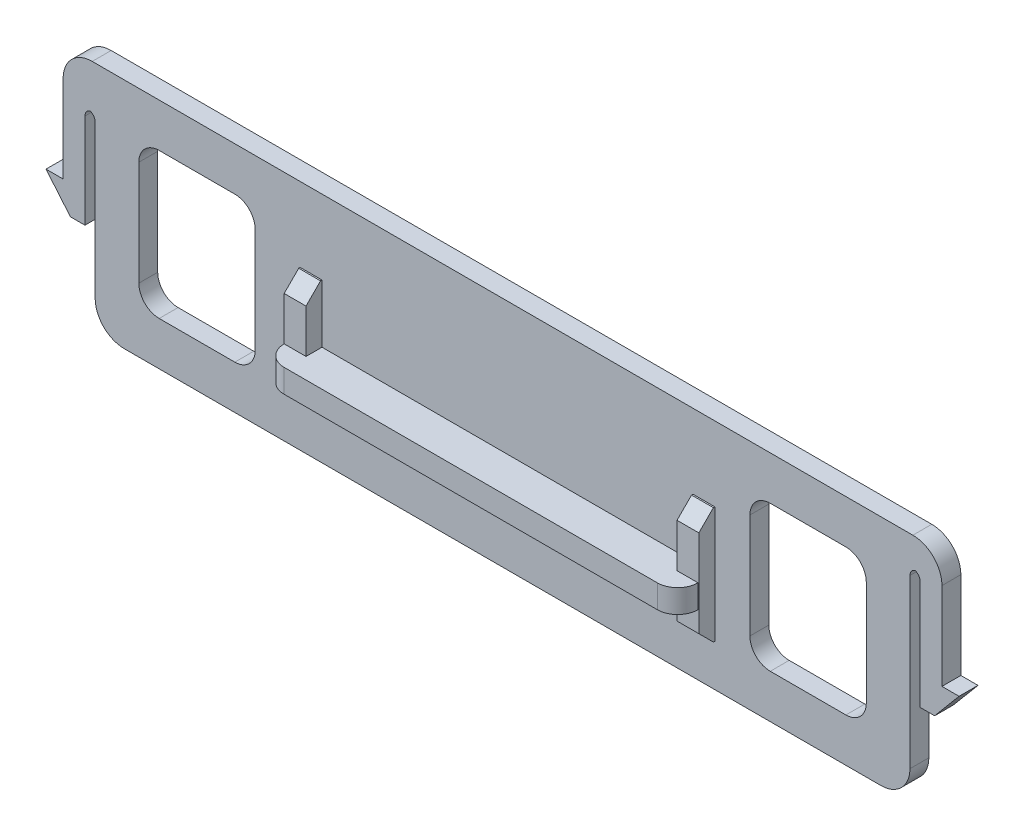
SolidWorks part; units mm, degrees
ref_plane "前视基准面" through (0, 0, 0) normal (0, 0, 1) x (1, 0, 0)
ref_plane "上视基准面" through (0, 0, 0) normal (0, 1, 0) x (1, 0, 0)
ref_plane "右视基准面" through (0, 0, 0) normal (1, 0, 0) x (0, 0, -1)
sketch "草图1" plane through (0, 0, 0) normal (0, 0, 1) x (1, 0, 0)
  line L1 (-28, 8) -> (28, 8)
  line L2 (-28, 8) -> (-28, -8)
  line L3 (-28, -8) -> (28, -8)
  line L4 (28, 8) -> (28, -8)
  line L5 (-28, 8) -> (28, -8) construction
  line L6 (-28, -8) -> (28, 8) construction
  point P0 (0, 0)
  dimension "D1" = 56
  dimension "D2" = 16
extrude "凸台-拉伸1" add sketch "草图1" along normal blind 1.3
sketch "草图2" plane through (0, 0, 1.3) normal (0, 0, 1) x (1, 0, 0)
  line L9 (28, 8) -> (30.2, 8)
  line L10 (30.2, 8) -> (30.2, 0)
  line L11 (30.2, 0) -> (31.7, 0)
  line L12 (31.7, 0) -> (31.7, -2)
  line L13 (31.7, -2) -> (28.7, -2)
  line L14 (28.7, -2) -> (28.7, 6)
  line L15 (28.7, 6) -> (28, 6)
  line L16 (28, -8) -> (28, 8) construction
  line L17 (28, 6) -> (28, 8)
  line L20 (-28, 8) -> (-30.2, 8)
  line L21 (-30.2, 8) -> (-30.2, 0)
  line L22 (-30.2, 0) -> (-31.7, 0)
  line L23 (-31.7, 0) -> (-31.7, -2)
  line L24 (-31.7, -2) -> (-28.7, -2)
  line L25 (-28.7, -2) -> (-28.7, 5)
  line L26 (-28.7, 5) -> (-28, 5)
  line L27 (-28, 8) -> (-28, -8) construction
  line L28 (-28, 5) -> (-28, 8)
  point P2 (0, 0)
  point P12 (-29, 6)
  point P23 (0, 0)
  point P24 (0, 0)
  dimension "D1" = 8
  dimension "D2" = 2
  dimension "D3" = 3
  dimension "D4" = 1.5
  dimension "D5" = 2.2
  dimension "D6" = 1.5
  dimension "D7" = 2.2
  dimension "D8" = 8
  dimension "D9" = 2
  dimension "D10" = 3
  dimension "D11" = 3
  dimension "D12" = 2
extrude "凸台-拉伸2" add sketch "草图2" against normal up to surface (1.3 mm away) up to face at (0, 0, 0)
fillet "圆角1" radius 2 4 edges at (30.2, 8, 0.65) (28, -8, 0.65) (-28, -8, 0.65) (-30.2, 8, 0.65)
fillet "圆角2" radius 0.5 4 edges at (28, 6, 0.65) (28.7, 6, 0.65) (-28, 5, 0.65) (-28.7, 5, 0.65)
chamfer "倒角1" distance 2 angle 50 1 edges at (31.7, -2, 0.65) first distance on face at (30.2, -2, 0.65)
chamfer "倒角2" distance 2 angle 50 1 edges at (-31.7, -2, 0.65) first distance on face at (-30.2, -2, 0.65)
sketch "草图3" plane through (0, 0, 1.3) normal (0, 0, 1) x (1, 0, 0)
  line L1 (-13.9089, 2.8832) -> (-12.4089, 2.8832)
  line L2 (-13.9089, 2.8832) -> (-13.9089, -5.1168)
  line L3 (-13.9089, -5.1168) -> (-12.4089, -5.1168)
  line L4 (-12.4089, 2.8832) -> (-12.4089, -5.1168)
  line L5 (13.0911, -5.1168) -> (14.5911, -5.1168)
  line L6 (13.0911, -5.1168) -> (13.0911, 2.8832)
  line L7 (13.0911, 2.8832) -> (14.5911, 2.8832)
  line L8 (14.5911, -5.1168) -> (14.5911, 2.8832)
extrude "凸台-拉伸3" add sketch "草图3" along normal blind 1.1
chamfer "倒角3" distance 1 angle 45 4 edges at (13.8411, -5.1168, 2.4) (-13.1589, -5.1168, 2.4) (13.8411, 2.8832, 2.4) (-13.1589, 2.8832, 2.4)
sketch "草图4" plane through (0, 0, 1.3) normal (0, 0, 1) x (1, 0, 0)
  line L0 (-13.9089, 1.8832) -> (-13.9089, -4.1168) construction
  line L1 (-13.9089, -1.1168) -> (14.5366, -1.1168)
  line L2 (-13.9089, -1.1168) -> (-13.9089, -2.7168)
  line L3 (-13.9089, -2.7168) -> (14.5366, -2.7168)
  line L4 (14.5366, -1.1168) -> (14.5366, -2.7168)
  point P8 (0, 0)
  dimension "D1" = 1.6
extrude "凸台-拉伸4" add sketch "草图4" along normal blind 2.5
fillet "圆角3" radius 1.4 2 edges at (14.5366, -1.9168, 3.8) (-13.9089, -1.9168, 3.8)
sketch "草图6" plane through (0, 0, 1.3) normal (0, 0, 1) x (1, 0, 0)
  line L0 (-28, 4.5) -> (-28, -6) construction
  line L1 (-25, 5) -> (-17, 5)
  line L2 (-25, 5) -> (-25, -5)
  line L3 (-25, -5) -> (-17, -5)
  line L4 (-17, 5) -> (-17, -5)
  line L5 (-25, 5) -> (-17, -5) construction
  line L6 (-25, -5) -> (-17, 5) construction
  line L7 (17, 5) -> (25, 5)
  line L8 (17, 5) -> (17, -5)
  line L9 (17, -5) -> (25, -5)
  line L10 (25, 5) -> (25, -5)
  line L11 (17, 5) -> (25, -5) construction
  line L12 (17, -5) -> (25, 5) construction
  line L13 (28, -6) -> (28, 5.5) construction
  line L14 (28.2, 8) -> (-28.2, 8) construction
  point P0 (-21, 0)
  point P5 (21, 0)
  dimension "D1" = 7
  dimension "D2" = 7
  dimension "D3" = 8
  dimension "D4" = 8
  dimension "D5" = 10
  dimension "D6" = 10
  dimension "D7" = 8
  dimension "D8" = 8
extrude "切除-拉伸1" cut sketch "草图6" against normal up to next
fillet "圆角4" radius 1.4 8 edges at (25, 5, 0.65) (17, 5, 0.65) (25, -5, 0.65) (17, -5, 0.65) (-17, -5, 0.65) (-25, -5, 0.65) (-17, 5, 0.65) (-25, 5, 0.65)
